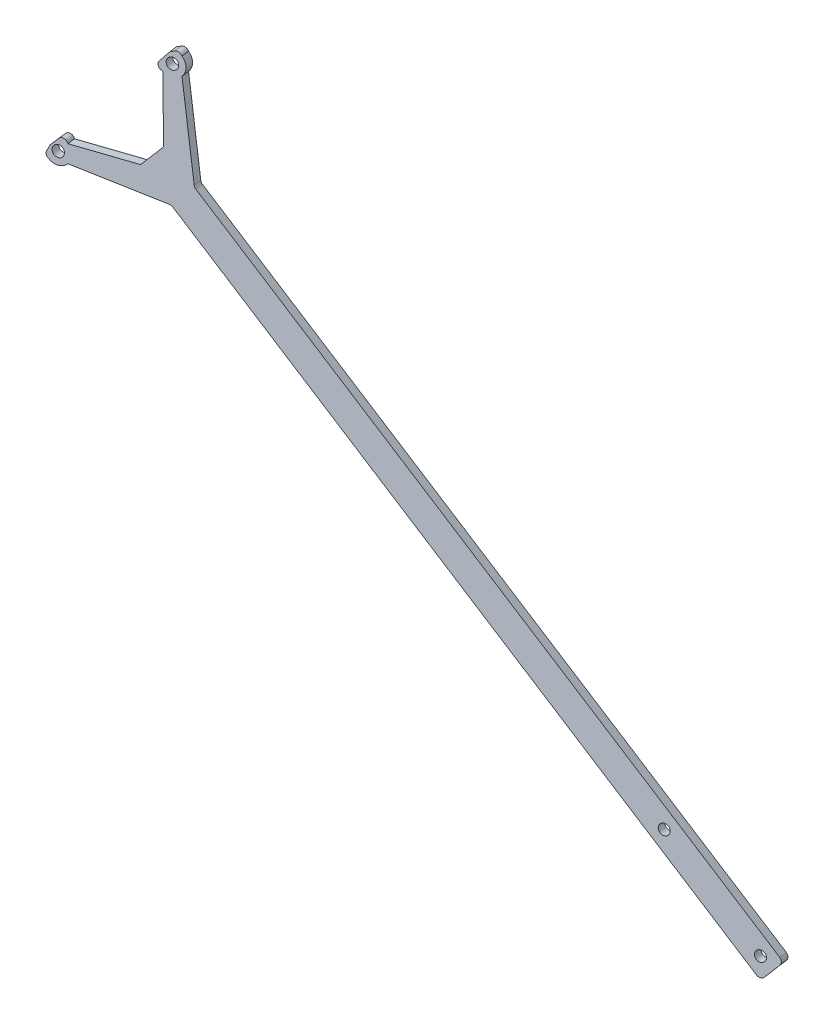
SolidWorks part; units mm, degrees
ref_plane "Płaszczyzna przednia" through (0, 0, 0) normal (0, 0, 1) x (1, 0, 0)
ref_plane "Płaszczyzna górna" through (0, 0, 0) normal (0, 1, 0) x (1, 0, 0)
ref_plane "Płaszczyzna prawa" through (0, 0, 0) normal (1, 0, 0) x (0, 0, -1)
sketch "Szkic3" plane through (38.1606, 20.2078, 157.3093) normal (0.2339, 0.1239, 0.9643) x (0.9723, -0.0298, -0.232)
  line L0 (-69.6663, -102.5536) -> (-79.2649, -94.7824) construction
  line L1 (-75.4894, -90.1192) -> (-65.8909, -97.8903) construction
  line L2 (-69.6663, -102.5536) -> (-79.2649, -94.7824)
  line L3 (-75.4894, -90.1192) -> (-65.8909, -97.8903)
  line L4 (-65.8909, -97.8903) -> (-52.9501, -108.3673)
  line L5 (-52.9501, -108.3673) -> (-56.7256, -113.0306)
  line L6 (-56.7256, -113.0306) -> (-69.6663, -102.5536)
  line L7 (-80.8192, -93.524) -> (-77.0437, -88.8608)
  line L8 (-77.0437, -88.8608) -> (-75.4894, -90.1192)
  line L9 (-80.8192, -93.524) -> (-79.2649, -94.7824)
  circle A2 centre (-57.1693, -108.811) radius 1.1 construction
  circle A3 centre (-76.5997, -93.08) radius 1.1 construction
  circle A6 centre (-57.1693, -108.811) radius 1.1
  circle A7 centre (-76.5997, -93.08) radius 1.1
  dimension "D1" = 6
  dimension "D2" = 6
  dimension "D3" = 3
  dimension "D4" = 3
extrude "Dodanie-wyciągnięcie2" add sketch "Szkic3" along normal blind 2
sketch "Szkic7" plane through (38.6285, 20.4556, 159.238) normal (0.2339, 0.1239, 0.9643) x (0.9723, -0.0298, -0.232)
  line L0 (-80.8192, -93.524) -> (-175.6389, -16.7567)
  line L1 (-181.8566, -11.7228) -> (-178.0811, -7.0595)
  line L2 (-171.8634, -12.0934) -> (-77.0437, -88.8608)
  line L3 (-80.8192, -93.524) -> (-56.7256, -113.0306) construction
  line L4 (-52.9501, -108.3673) -> (-77.0437, -88.8608) construction
  line L5 (-77.0437, -88.8608) -> (-80.8192, -93.524) construction
  line L6 (-198.2737, -16.8303) -> (-199.4913, -17.3886) construction
  line L7 (-195.6167, -11.1329) -> (-195.1275, -12.9443) construction
  line L8 (-176.2094, 11.3682) -> (-176.502, 10.0611) construction
  line L9 (-179.6482, 6.1751) -> (-181.5217, 6.2766) construction
  line L10 (-198.2737, -16.8303) -> (-199.4913, -17.3886)
  line L11 (-195.6167, -11.1329) -> (-195.1275, -12.9443)
  line L12 (-176.2094, 11.3682) -> (-176.502, 10.0611)
  line L13 (-179.6482, 6.1751) -> (-181.5217, 6.2766)
  line L14 (-199.4913, -17.3886) -> (-198.2737, -14.3498)
  line L15 (-198.2737, -14.3498) -> (-195.6167, -11.1329)
  line L16 (-176.2094, 11.3682) -> (-178.719, 10.0611)
  line L17 (-178.719, 10.0611) -> (-181.5217, 6.2766)
  line L18 (-194.7574, -16.4605) -> (-175.6389, -16.7567)
  line L19 (-195.1275, -12.9443) -> (-181.8566, -11.7228)
  line L20 (-178.0811, -7.0595) -> (-179.6482, 6.1751)
  line L21 (-176.1319, 6.5449) -> (-171.8634, -12.0934)
  line L22 (-80.8192, -93.524) -> (-77.0437, -88.8608)
  circle A0 centre (-178.075, 8.118) radius 1.15 construction
  circle A1 centre (-196.7005, -14.8874) radius 1.15 construction
  circle A2 centre (-178.075, 8.118) radius 1.15
  circle A3 centre (-196.7005, -14.8874) radius 1.15
  arc A4 (-198.2737, -16.8303) -> (-194.7574, -16.4605) centre (-196.7005, -14.8874) ccw
  arc A5 (-176.1319, 6.5449) -> (-176.502, 10.0611) centre (-178.075, 8.118) ccw
  dimension "D1" = 130
  dimension "D2" = 8
  dimension "D3" = 8
extrude "Dodanie-wyciągnięcie4" add sketch "Szkic7" against normal blind 2
fillet "Zaokrąglenie1" radius 1 8 edges at (-151.7944, 15.12, 205.0798) (-155.5615, 9.0308, 206.7759) (-138.0905, 31.9675, 199.5913) (-132.9256, 36.8593, 197.71) (-132.3709, 8.9466, 201.161) (-128.7002, 13.4593, 199.6909) (-13.0864, -85.5742, 184.3666) (-16.7571, -90.0869, 185.8368)
